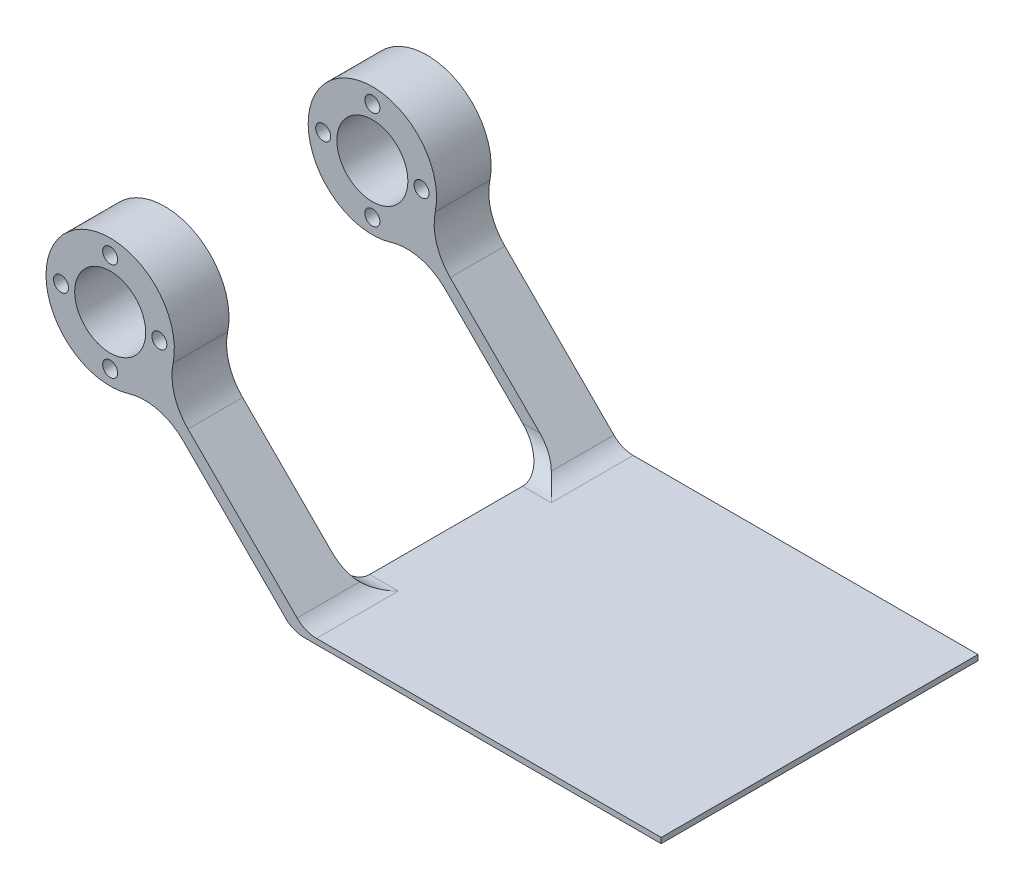
SolidWorks part; units mm, degrees
note: '?' marks a value the reader was unsure of.
material "ABS"
ref_plane "Front" through (0, 0, 0) normal (0, 0, 1) x (1, 0, 0)
ref_plane "Top" through (0, 0, 0) normal (0, 1, 0) x (1, 0, 0)
ref_plane "Right" through (0, 0, 0) normal (1, 0, 0) x (0, 0, -1)
other "Center of Mass"
sketch "Sketch30" plane through (0, 0, 0) normal (0, 1, 0) x (1, 0, 0)
  line L0 (-19.2967, 23.7319) -> (-104.205, 23.7319)
  line L1 (-19.2967, -11.2303) -> (-19.2967, 23.7319)
  line L2 (-29.2859, -21.2195) -> (-104.205, -21.2195)
  line L3 (-113.877, 16.24) -> (-113.877, 58)
  line L4 (-113.877, 58) -> (113.877, 58)
  line L5 (113.877, 58) -> (113.877, -58)
  line L6 (113.877, -58) -> (-113.877, -58)
  line L7 (-113.877, -58) -> (-113.877, -13.7276)
  arc A0 (-104.205, 23.7319) -> (-113.877, 16.24) centre (-104.205, 13.7427) ccw
  arc A1 (-29.2859, -21.2195) -> (-19.2967, -11.2303) centre (-29.2859, -11.2303) ccw
  arc A2 (-113.877, -13.7276) -> (-104.205, -21.2195) centre (-104.205, -11.2303) ccw
  dimension "D1" = 116
extrude "Boss-Extrude13" add sketch "Sketch30" along normal blind 2
fillet "Fillet1" radius 10 2 edges at (-113.877, 0, -37.12) (-113.877, 0, 35.8638)
sketch "Sketch31" plane through (0, 0, 58) normal (0, 0, 1) x (1, 0, 0)
  line L0 (-113.877, 2) -> (-168.877, 57)
  line L1 (-168.877, 57) -> (-165.695, 60.182)
  line L2 (-165.695, 60.182) -> (-107.5131, 2)
  line L3 (-113.877, 2) -> (113.877, 2) construction
  line L7 (113.877, 2) -> (-113.877, 2)
  line L8 (-107.877, 0) -> (113.877, 0)
  line L9 (113.877, 0) -> (113.877, 2)
  line L10 (113.877, 2) -> (-107.5131, 2)
  line L11 (-107.877, 0) -> (113.877, 0)
  line L12 (113.877, 0) -> (113.877, 2)
  arc A1 (-113.877, 2) -> (-107.877, 0) centre (-107.877, 10) ccw
  arc A2 (-113.877, 2) -> (-107.877, 0) centre (-107.877, 10) ccw
  dimension "D1" = 45
  dimension "D2" = 4.5
  dimension "D3" = 55
  dimension "D4" = 0
extrude "Boss-Extrude14" add sketch "Sketch31" against normal blind 20
fillet "Fillet2" radius 10 1 edges at (-110.695, 2, 38)
fillet "Fillet3" radius 10 1 edges at (-107.5131, 2, 43)
sketch "Sketch32" plane through (0, 0, 0) normal (0, 0, 1) x (1, 0, 0)
  line L0 (-183.5235, 72.3536) -> (-108.1047, -2.9319) construction
  circle A0 centre (-178.8779, 67.7162) radius 23.5
  circle A1 centre (-196.8779, 67.7162) radius 2.75
  circle A2 centre (-178.8779, 85.7162) radius 2.75
  circle A3 centre (-160.8779, 67.7162) radius 2.75
  circle A4 centre (-178.8779, 49.7162) radius 2.75
  circle A5 centre (-178.8779, 67.7162) radius 13
  dimension "D2" = 47
  dimension "D3" = 18
  dimension "D4" = 5.5
  dimension "D6" = 5.5
  dimension "D9" = 5.5
  dimension "D10" = 5.5
  dimension "D11" = 26
  dimension "D1" = 100
  dimension "D5" = 18
  dimension "D7" = 18
  dimension "D8" = 18
extrude "Boss-Extrude16" add sketch "Sketch32" along normal through all
mirror "Mirror1" of "Boss-Extrude14", "Boss-Extrude16"
fillet "Fillet6" radius 10 2 edges at (-110.695, 2, -38) (-107.5131, 2, -48)
sketch "Sketch37" plane through (0, 0, 0) normal (0, 1, 0) x (1, 0, 0)
  line L0 (-103.3709, -36) -> (-103.3709, 28)
  line L1 (-103.3709, -36) -> (-103.3709, -58)
  dimension "D1" = 22
  dimension "D2" = 64
ref_point "Point1"
sketch "Sketch38" plane through (0, 0, 0) normal (0, 0, 1) x (1, 0, 0)
  line L0 (0, 0) -> (0, 98.5948) construction
  line L1 (0, 0) -> (160.664, 0) construction
sketch "Sketch39" plane through (0, 0, 0) normal (1, 0, 0) x (0, 0, -1)
  line L0 (-0.2484, 0) -> (124.0325, 0) construction
ref_axis "Axis2" through (-178.8779, 67.7162, 58) along (0, 0, -1)?
fillet "Fillet7" radius 20 4 edges at (-162.6224, 50.7454, 48) (-162.6224, 50.7454, -48) (-159.6783, 54.1653, -48) (-159.6783, 54.1653, 48)
sketch "Sketch40" plane through (0, 0, 0) normal (0, 0, 1) x (1, 0, 0)
  circle A0 centre (-178.8779, 67.7162) radius 23.5
  dimension "D1" = 47
extrude "Cut-Extrude1" cut sketch "Sketch40" against normal blind 35 and the other way blind 35
sketch "Sketch41" plane through (0, 0, 58) normal (0, 0, 1) x (1, 0, 0)
  line L0 (-178.8779, 67.7162) -> (-113.398, 2.2363) construction
  dimension "D1" = 65.4799
sketch "Sketch42" plane through (0, 0, 35) normal (0, 0, -1) x (-1, 0, 0)
  circle A0 centre (179.4941, 67.541) radius 26.4456
extrude "Cut-Extrude2" cut sketch "Sketch42" against normal up to vertex (13 mm away)
sketch "Sketch43" plane through (0, 0, -35) normal (0, 0, 1) x (1, 0, 0)
  circle A0 centre (-177.0232, 70.5655) radius 28.2819
extrude "Cut-Extrude3" cut sketch "Sketch43" against normal up to vertex (3 mm away)
sketch "Sketch44" plane through (0, 2, 0) normal (0, 1, 0) x (1, 0, 0)
  line L1 (113.877, 58) -> (-103.3709, 58) construction
  line L3 (113.877, -58) -> (22.877, -58)
  line L4 (113.877, -58) -> (113.877, 58)
  line L5 (113.877, 58) -> (22.877, 58)
  line L6 (22.877, -58) -> (22.877, 58)
  dimension "D1" = 91
extrude "Cut-Extrude4" cut sketch "Sketch44" against normal up to surface (2 mm away) up to face at (-43.4582, 0, 0.5238)
sketch "Sketch48" plane through (0, 2, 0) normal (0, 1, 0) x (1, 0, 0)
  line L1 (-15.7957, -22.8032) -> (-113.877, -22.8032)
  line L2 (-15.7957, -22.8032) -> (-15.7957, 28)
  line L3 (-15.7957, 28) -> (-113.877, 28)
  line L4 (-113.877, -22.8032) -> (-113.877, 28)
extrude "Boss-Extrude17" add sketch "Sketch48" against normal up to surface (2 mm away) up to face at (-60.0037, 0, 0.5238)
fillet "Fillet8" radius 10 1 edges at (-113.877, 0, -2.5984)
